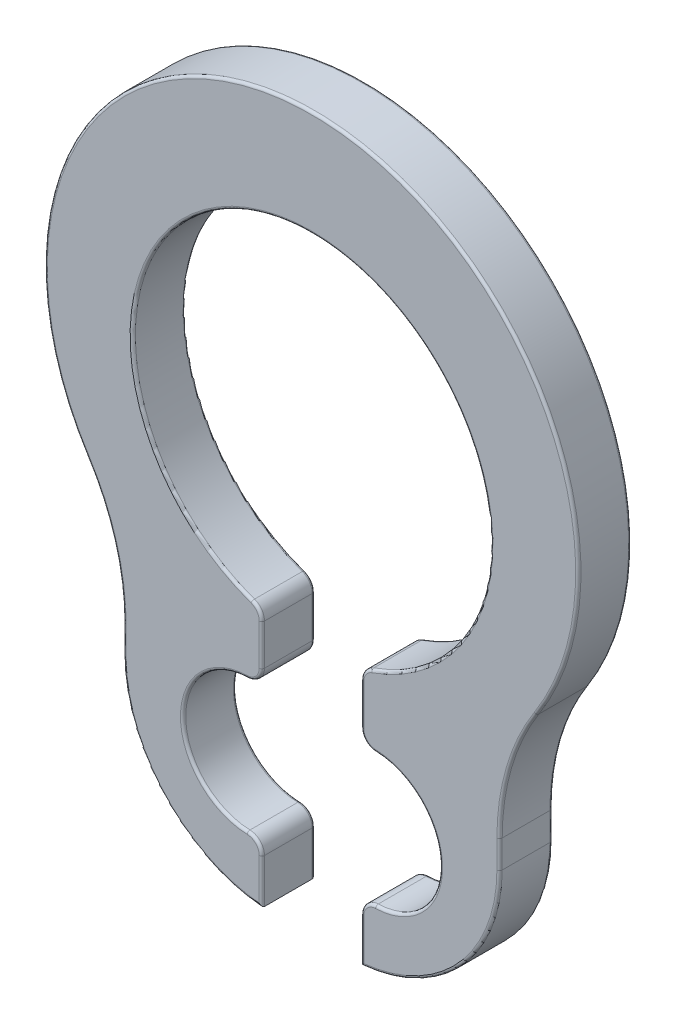
SolidWorks part; units mm, degrees
ref_plane "Front Plane" through (0, 0, 0) normal (0, 0, 1) x (1, 0, 0)
ref_plane "Top Plane" through (0, 0, 0) normal (0, 1, 0) x (1, 0, 0)
ref_plane "Right Plane" through (0, 0, 0) normal (1, 0, 0) x (0, 0, -1)
sketch "Sketch1" plane through (0, 0, 0) normal (0, 0, 1) x (1, 0, 0)
  line L0 (0, 2.7) -> (0, -2.7) construction
  line L1 (-0.47, -1.75) -> (0.47, -1.75) construction
  line L2 (-0.47, -1.25) -> (0.47, -1.25)
  line L3 (-0.47, -2.25) -> (0.47, -2.25)
  line L4 (0.97, -1.75) -> (1.42, -1.75) construction
  line L5 (0, -0.8) -> (0, -1.25) construction
  circle A0 centre (0, 0.55) radius 1.35
  arc A3 (-0.47, -1.25) -> (-0.47, -2.25) centre (-0.47, -1.75) ccw
  arc A4 (0.47, -2.25) -> (0.47, -1.25) centre (0.47, -1.75) ccw
  circle A5 centre (0, 0.685) radius 2.015 construction
  circle A6 centre (0, 0.55) radius 1.5 construction
  circle A7 centre (0, 0.55) radius 1.4 construction
  point P6 (0, 1.9)
  point P7 (0, -0.8)
  point P10 (0, -1.75)
  dimension "For OD" = 3
  dimension "ID" = 2.7
  dimension "Band Width" = 0.8
  dimension "Tap Height" = 1.9
  dimension "Tap ID" = 1
  dimension "D3" = 0.95
  dimension "Tap Width Ref" = 2.84
  dimension "D1" = 0.135
sketch "Sketch2" plane through (0, 0, 0) normal (1, 0, 0) x (0, 0, -1)
  line L0 (-0.2, 2.7) -> (0.2, 2.7) construction
  line L1 (0, 3.8) -> (0, -2.7) construction
  line L2 (0, 2.7) -> (0, -2.7) construction
  line L3 (-0.25, 3.8) -> (0.25, 3.8) construction
  line L4 (-0.25, -2.7) -> (0.25, -2.7) construction
  dimension "Thickness" = 0.4
  dimension "For Groove Width" = 0.5
sketch "Sketch3" plane through (0, 0, 0) normal (0, 0, 1) x (1, 0, 0)
  line L0 (-0.47, -2.25) -> (0.47, -2.25) construction
  line L1 (-0.47, -1.25) -> (0.47, -1.25) construction
  line L2 (-0.47, -2.25) -> (0.47, -2.25)
  line L3 (-0.47, -1.25) -> (0.47, -1.25)
  line L4 (1.42, -1.3503) -> (1.42, -1.56)
  line L5 (-0.28, -2.7) -> (0.28, -2.7)
  line L6 (-1.42, -1.3503) -> (-1.42, -1.56)
  line L7 (-0.97, -1.75) -> (-1.42, -1.75) construction
  line L8 (0.97, -1.75) -> (1.42, -1.75) construction
  arc A0 (-0.47, -1.25) -> (-0.47, -2.25) centre (-0.47, -1.75) ccw construction
  arc A1 (0.47, -2.25) -> (0.47, -1.25) centre (0.47, -1.75) ccw construction
  arc A2 (-0.47, -1.25) -> (-0.47, -2.25) centre (-0.47, -1.75) ccw
  arc A3 (0.47, -2.25) -> (0.47, -1.25) centre (0.47, -1.75) ccw
  circle A4 centre (0, 0.55) radius 1.35 construction
  circle A5 centre (0, 0.55) radius 1.35
  arc A6 (-1.6977, -0.4003) -> (1.6977, -0.4003) centre (0, 0.685) cw
  arc A8 (1.6977, -0.4003) -> (1.42, -1.3503) centre (3.1837, -1.3503) ccw
  arc A9 (1.42, -1.56) -> (0.28, -2.7) centre (0.28, -1.56) cw
  arc A10 (-1.6977, -0.4003) -> (-1.42, -1.3503) centre (-3.1837, -1.3503) cw
  arc A11 (-1.42, -1.56) -> (-0.28, -2.7) centre (-0.28, -1.56) ccw
  circle A12 centre (0, 0.685) radius 2.015 construction
  dimension "D1" = 0.95
  dimension "D2" = 1.14
  dimension "D3" = 0.45
extrude "Boss-Extrude1" add sketch "Sketch3" along normal mid plane 0.4
sketch "Sketch4" plane through (0, 0, 0) normal (0, 0, 1) x (1, 0, 0)
  line L0 (0, 0.55) -> (0, -2.7)
extrude "Cut-Extrude-Thin1" cut sketch "Sketch4" against normal through all both and the other way through all thin thin type mid plane wall 0.75
fillet "Fillet2" radius 0.1125 6 edges at (0.375, -2.25, 0) (-0.375, -2.25, 0) (0.375, -1.25, 0) (0.375, -0.7469, 0) (-0.375, -1.25, 0) (-0.375, -0.7469, 0)
fillet "Fillet1" radius 0.02 40 edges at (-0.97, -1.75, -0.2) (0, 1.9, -0.2) (0.97, -1.75, -0.2) (1.119, -2.3318, -0.2) (1.42, -1.4552, -0.2) (1.4909, -0.8555, -0.2) (0, 2.7, -0.2) (-1.4909, -0.8555, -0.2) (-1.42, -1.4552, -0.2) (-1.119, -2.3318, -0.2) (-1.119, -2.3318, 0.2) (-1.42, -1.4552, 0.2) (-1.4909, -0.8555, 0.2) (0, 2.7, 0.2) (1.4909, -0.8555, 0.2) (1.42, -1.4552, 0.2) (1.119, -2.3318, 0.2) (0.97, -1.75, 0.2) (0, 1.9, 0.2) (-0.97, -1.75, 0.2) (-0.4068, -2.2838, -0.2) (-0.4068, -1.2162, -0.2) (-0.375, -0.9833, -0.2) (-0.3956, -0.7639, -0.2) (0.3956, -0.7639, -0.2) (0.375, -0.9833, -0.2) (0.4068, -1.2162, -0.2) (0.4068, -2.2838, -0.2) (0.4068, -1.2162, 0.2) (0.375, -0.9833, 0.2) (0.3956, -0.7639, 0.2) (-0.3956, -0.7639, 0.2) (-0.375, -0.9833, 0.2) (-0.4068, -1.2162, 0.2) (-0.4068, -2.2838, 0.2) (0.4068, -2.2838, 0.2) (-0.375, -2.5291, -0.2) (0.375, -2.5291, -0.2) (-0.375, -2.5291, 0.2) (0.375, -2.5291, 0.2)
equation "\"D3@Sketch1\"=\"Tap Height@Sketch1\"*0.5"
equation "\"D1@Sketch3\"=\"Tap Height@Sketch1\"*0.5"
equation "\"D2@Sketch3\"=\"Tap Height@Sketch1\"*0.6"
equation "\"D1@Boss-Extrude1\" = \"Thickness@Sketch2\""
equation "\"D1@Sketch1\"= \"ID@Sketch1\" * 0.05"
equation "\"D1@Fillet2\"=\"D3@Sketch3\"*0.25"
